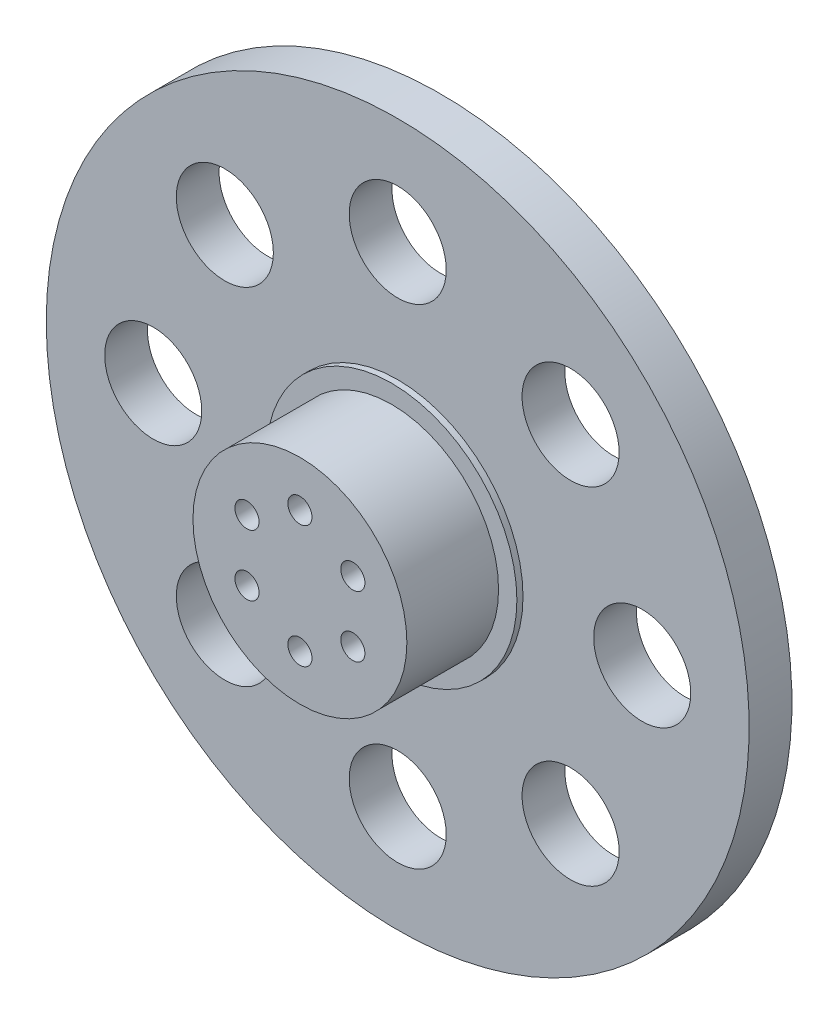
SolidWorks part; units mm, degrees
material "PETG"
ref_plane "Front Plane" through (0, 0, 0) normal (0, 0, 1) x (1, 0, 0)
ref_plane "Top Plane" through (0, 0, 0) normal (0, 1, 0) x (1, 0, 0)
ref_plane "Right Plane" through (0, 0, 0) normal (1, 0, 0) x (0, 0, -1)
sketch "Sketch1" plane through (0, 0, 0) normal (0, 0, 1) x (1, 0, 0)
  circle A0 centre (0, 0) radius 17.5
  dimension "D1" = 35
extrude "Boss-Extrude1" add sketch "Sketch1" along normal blind 15
sketch "Sketch7" plane through (0, 0, 0) normal (0, 0, -1) x (-1, 0, 0)
  circle A0 centre (0, 0) radius 20.5
  dimension "D1" = 41
extrude "Boss-Extrude3" add sketch "Sketch7" along normal blind 1
sketch "Sketch3" plane through (0, 0, -1) normal (0, 0, -1) x (-1, 0, 0)
  circle A0 centre (0, 0) radius 57.5
  dimension "D1" = 115
extrude "Boss-Extrude2" add sketch "Sketch3" along normal blind 7
sketch "Sketch4" plane through (0, 0, -8) normal (0, 0, -1) x (-1, 0, 0)
  circle A0 centre (0, 0) radius 11
  dimension "D1" = 22
extrude "Cut-Extrude1" cut sketch "Sketch4" against normal blind 7
sketch "Sketch5" plane through (0, 0, -1) normal (0, 0, -1) x (-1, 0, 0)
  circle A0 centre (0, 0) radius 7.5
  dimension "D1" = 15
extrude "Cut-Extrude2" cut sketch "Sketch5" against normal blind 0.5
sketch "Sketch6" plane through (0, 0, 15) normal (0, 0, 1) x (1, 0, 0)
  circle A0 centre (0, 10) radius 1.975
  dimension "D1" = 3.95
  dimension "D2" = 10
extrude "Cut-Extrude3" cut sketch "Sketch6" against normal blind 6
pattern_circular "CirPattern1" count 6 over 360 about axis through (0, 0, 15) along (0, 0, 1) of "Cut-Extrude3"
sketch "Sketch8" plane through (0, 0, -1) normal (0, 0, 1) x (1, 0, 0)
  circle A0 centre (0, 0) radius 40 construction
  circle A1 centre (-40, 0) radius 7.94
  circle A2 centre (-28.2843, 28.2843) radius 7.94
  circle A3 centre (0, 40) radius 7.94
  circle A4 centre (28.2843, 28.2843) radius 7.94
  circle A5 centre (40, 0) radius 7.94
  circle A6 centre (28.2843, -28.2843) radius 7.94
  circle A7 centre (0, -40) radius 7.94
  circle A8 centre (-28.2843, -28.2843) radius 7.94
  dimension "D1" = 80
  dimension "D2" = 15.88
  dimension "D3" = 8
extrude "Cut-Extrude4" cut sketch "Sketch8" against normal through all
equation "\"N\"= 21"
equation "\"R\"= 65mm"
equation "\"E\" = ROUND(\"R\" / \"N\" * 0.7, 2)"
equation "\"R_r\" = ( 1in / 2 ) / 2"
equation "\"D_p\" = 8cm"
equation "\"D1@Sketch8\"=\"D_p\""
equation "\"N_p\"= 8"
equation "\"D3@Sketch8\"=\"N_p\""
